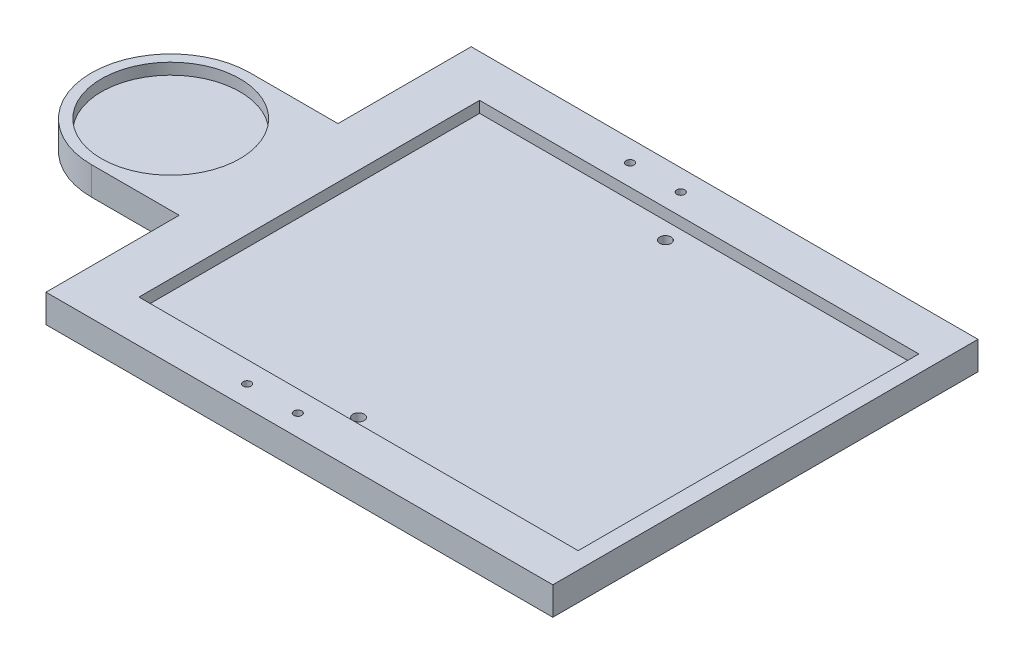
SolidWorks part; units mm, degrees
note: The reader was unsure of these and kept them because the rebuilt part matched: shared geometry of "Sketch1<4>".
material "Pine"
ref_plane "Front Plane" through (0, 0, 0) normal (0, 0, 1) x (1, 0, 0)
ref_plane "Top Plane" through (0, 0, 0) normal (0, 1, 0) x (1, 0, 0)
ref_plane "Right Plane" through (0, 0, 0) normal (1, 0, 0) x (0, 0, -1)
sketch "Sketch1" plane through (0, 0, 0) normal (0, 1, 0) x (1, 0, 0)
  line L0 (0, 188.75) -> (450, 188.75)
  line L1 (450, 188.75) -> (450, -188.75)
  line L2 (450, -188.75) -> (0, -188.75)
  line L3 (0, -188.75) -> (0, -70.5)
  line L4 (0, 70.5) -> (0, 188.75)
  line L5 (0, -70.5) -> (-78, -70.5)
  line L6 (-78, 70.5) -> (0, 70.5)
  line L7 (0, 0) -> (434.6552, 0) construction
  line L8 (435, -151.25) -> (45, -151.25)
  line L9 (435, -151.25) -> (435, 151.25)
  line L10 (435, 151.25) -> (45, 151.25)
  line L11 (45, -151.25) -> (45, 151.25)
  line L12 (435, -151.25) -> (45, 151.25) construction
  line L13 (435, 151.25) -> (45, -151.25) construction
  arc A1 (-78, -70.5) -> (-78, 70.5) centre (-78, 0) cw
  circle A2 centre (-78, 0) radius 61.5
  circle A3 centre (225, 136.25) radius 5
  circle A4 centre (225, -136.25) radius 5
  point P4 (450, 0)
  point P10 (240, 0)
  point P24 (225, 188.75)
  dimension "D3" = 70.5
  dimension "D5" = 390
  dimension "D8" = 123
  dimension "D9" = 10
  dimension "D10" = 15
  dimension "D1" = 450
  dimension "D2" = 377.5
  dimension "D4" = 78
  dimension "D6" = 302.5
  dimension "D7" = 15
extrude "Boss-Extrude1" add sketch "Sketch1" along normal blind 25 contours A1 L5 L3 L2 L1 L0 L4 L6 A2 L8 L11 L10 L9 | A2 | L11 L8 L9 L10 A3 A4
extrude "Boss-Extrude2" add sketch "Sketch1<4>" along normal blind 15 contours L11 L8 L9 L10 A3 A4 | A2
sketch "Sketch1<4>" plane through (0, 0, 0) normal (0, 1, 0) x (1, 0, 0) same geometry as "Sketch1"
sketch "Sketch2" plane through (0, 25, 0) normal (0, 1, 0) x (1, 0, 0)
  line L0 (440, 188.75) -> (440, -188.75) construction
  line L1 (0, 188.75) -> (450, 188.75) construction
  line L2 (450, -188.75) -> (0, -188.75) construction
  line L3 (450, 188.75) -> (450, -188.75) construction
  dimension "D1" = 10
sketch "Sketch3" plane through (0, 25, 0) normal (0, 1, 0) x (1, 0, 0)
  line L0 (0, -188.75) -> (0, -70.5) construction
  line L1 (154.1222, -151.25) -> (154.1222, -188.75) construction
  line L2 (435, -151.25) -> (45, -151.25) construction
  line L3 (450, -188.75) -> (0, -188.75) construction
  line L4 (0, 0) -> (522.9425, 0) construction
  circle A0 centre (159.81, -170) radius 3.5
  circle A1 centre (204.81, -170) radius 3.5
  circle A2 centre (204.81, 170) radius 3.5
  circle A3 centre (159.81, 170) radius 3.5
  point P13 (154.1222, -170)
  dimension "D1" = 7
  dimension "D2" = 7
  dimension "D3" = 159.81
  dimension "D4" = 45
extrude "Cut-Extrude1" cut sketch "Sketch3" against normal through all
